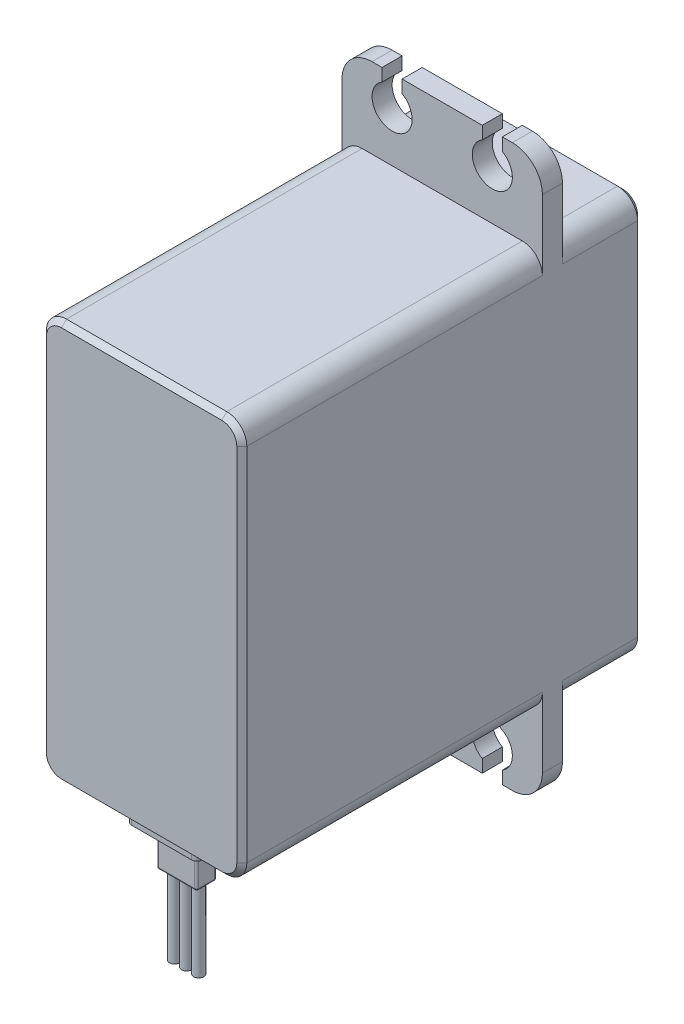
SolidWorks part; units mm, degrees
ref_plane "前视基准面" through (0, 0, 0) normal (0, 0, 1) x (1, 0, 0)
ref_plane "上视基准面" through (0, 0, 0) normal (0, 1, 0) x (1, 0, 0)
ref_plane "右视基准面" through (0, 0, 0) normal (1, 0, 0) x (0, 0, -1)
sketch "草图1" plane through (0, 0, 0) normal (0, 0, 1) x (1, 0, 0)
  line L1 (-10, -28) -> (10, -28)
  line L2 (-10, -28) -> (-10, 28)
  line L3 (-10, 28) -> (10, 28)
  line L4 (10, -28) -> (10, 28)
  line L5 (-10, -28) -> (10, 28) construction
  line L6 (-10, 28) -> (10, -28) construction
  point P0 (0, 0)
  dimension "D1" = 20
  dimension "D2" = 56
extrude "凸台-拉伸1" add sketch "草图1" along normal blind 40
sketch "草图2" plane through (0, 0, 40) normal (0, 0, 1) x (1, 0, 0)
  line L0 (10, -28) -> (10, 28) construction
  line L1 (-10, -20) -> (10, -20)
  line L2 (-10, -20) -> (-10, 20)
  line L3 (-10, 20) -> (10, 20)
  line L4 (10, -20) -> (10, 20)
  line L5 (-10, -20) -> (10, 20) construction
  line L6 (-10, 20) -> (10, -20) construction
  point P0 (0, 0)
  dimension "D1" = 40
extrude "切除-拉伸1" cut sketch "草图2" against normal blind 30 flip side to cut
extrude "切除-拉伸2" cut sketch "草图2<2>" along normal blind 8 from surface flip side to cut contours L2 L3 L4 L1 starting at face at (0, 0, 0)
sketch "草图2<2>" plane through (0, 0, 40) normal (0, 0, 1) x (1, 0, 0) same geometry as "草图2"
sketch "草图3" plane through (0, 0, 10) normal (0, 0, 1) x (1, 0, 0)
  line L0 (4, 26.7321) -> (4, 28)
  line L1 (10, 28) -> (-10, 28) construction
  line L2 (4, 28) -> (6, 28)
  line L3 (6, 28) -> (6, 26.7321)
  line L4 (5, 25) -> (5, 28) construction
  line L5 (10, 20) -> (10, 28) construction
  line L6 (-6, 26.7321) -> (-6, 28)
  line L7 (-6, 28) -> (-4, 28)
  line L8 (-4, 28) -> (-4, 26.7321)
  line L9 (0, 0) -> (15.7926, 0) construction
  line L10 (5, -25) -> (5, -28) construction
  line L11 (-4, -28) -> (-4, -26.7321)
  line L12 (-6, -28) -> (-4, -28)
  line L13 (-6, -26.7321) -> (-6, -28)
  line L14 (6, -28) -> (6, -26.7321)
  line L15 (4, -28) -> (6, -28)
  line L16 (4, -26.7321) -> (4, -28)
  arc A0 (4, 26.7321) -> (6, 26.7321) centre (5, 25) ccw
  arc A1 (-6, 26.7321) -> (-4, 26.7321) centre (-5, 25) ccw
  arc A2 (-6, -26.7321) -> (-4, -26.7321) centre (-5, -25) cw
  arc A3 (4, -26.7321) -> (6, -26.7321) centre (5, -25) cw
  dimension "D1" = 2
  dimension "D2" = 3
  dimension "D3" = 2
  dimension "D4" = 4
  dimension "D6" = 10
  dimension "D5" = 2
extrude "切除-拉伸3" cut sketch "草图3" against normal through all
sketch "草图4" plane through (0, -20, 0) normal (0, -1, 0) x (1, 0, 0)
  line L0 (-10, 40) -> (10, 40) construction
  line L1 (-3.5, 33) -> (3.5, 33)
  line L2 (-3.5, 33) -> (-3.5, 38)
  line L3 (-3.5, 38) -> (3.5, 38)
  line L4 (3.5, 33) -> (3.5, 38)
  line L5 (-3.5, 33) -> (3.5, 38) construction
  line L6 (-3.5, 38) -> (3.5, 33) construction
  point P0 (0, 35.5)
  dimension "D1" = 7
  dimension "D2" = 5
  dimension "D3" = 2
extrude "凸台-拉伸2" add sketch "草图4" along normal blind 2
sketch "草图5" plane through (0, -22, 0) normal (0, -1, 0) x (1, 0, 0)
  line L0 (-3.5, 38) -> (3.5, 33) construction
  line L1 (-2, 34.5) -> (2, 34.5)
  line L2 (-2, 34.5) -> (-2, 36.5)
  line L3 (-2, 36.5) -> (2, 36.5)
  line L4 (2, 34.5) -> (2, 36.5)
  line L5 (-2, 34.5) -> (2, 36.5) construction
  line L6 (-2, 36.5) -> (2, 34.5) construction
  line L7 (3.5, 38) -> (-3.5, 33) construction
  point P0 (0, 35.5)
  dimension "D1" = 4
  dimension "D2" = 2
extrude "凸台-拉伸3" add sketch "草图5" along normal blind 4
sketch "草图6" plane through (0, -26, 0) normal (0, -1, 0) x (1, 0, 0)
  line L0 (2, 34.5) -> (2, 36.5) construction
  line L1 (-2, 35.5) -> (2, 35.5) construction
  line L2 (-2, 36.5) -> (-2, 34.5) construction
  line L3 (2, 34.5) -> (2, 36.5) construction
  circle A0 centre (1.2, 35.5) radius 0.5
  circle A1 centre (0, 35.5) radius 0.5
  circle A2 centre (-1.2, 35.5) radius 0.5
  dimension "D1" = 1
  dimension "D2" = 0.8
  dimension "D4" = 1.2
  dimension "D3" = 1.2
extrude "凸台-拉伸4" add sketch "草图6" along normal blind 8
sketch "草图7" plane through (0, 0, 0) normal (0, 0, -1) x (-1, 0, 0)
  line L0 (-10, -20) -> (10, -20) construction
  circle A0 centre (0, -12) radius 6
  dimension "D1" = 12
  dimension "D2" = 8
extrude "凸台-拉伸5" add sketch "草图7" along normal blind 2
sketch "草图8" plane through (0, 0, -2) normal (0, 0, -1) x (-1, 0, 0)
  circle A0 centre (0, -12) radius 5
  dimension "D1" = 10
extrude "切除-拉伸4" cut sketch "草图8" against normal blind 0.8
sketch "草图9" plane through (0, 0, -1.2) normal (0, 0, -1) x (-1, 0, 0)
  circle A0 centre (0, -12) radius 2.5
  dimension "D1" = 5
extrude "切除-拉伸5" cut sketch "草图9" against normal blind 4
sketch "草图10" plane through (0, 0, 2.8) normal (0, 0, -1) x (-1, 0, 0)
  circle A1 centre (0, -12) radius 2.5
  circle A2 centre (0, -12) radius 2.5
  dimension "D1" = 0
extrude "凸台-拉伸6" add sketch "草图10" along normal blind 10 separate body
sketch "草图11" plane through (0, 0, -7.2) normal (0, 0, -1) x (-1, 0, 0)
  line L0 (0, -12) -> (0, -9.5) construction
  line L1 (0, -10) -> (-0.2796, -9.5157)
  line L2 (0, -10) -> (0.2796, -9.5157)
  line L3 (0.618, -10.0979) -> (0.5018, -9.5509)
  line L4 (0.618, -10.0979) -> (1.0336, -9.7237)
  line L5 (1.1756, -10.382) -> (1.234, -9.8258)
  line L6 (1.1756, -10.382) -> (1.6865, -10.1545)
  line L7 (1.618, -10.8244) -> (1.8455, -10.3135)
  line L8 (1.618, -10.8244) -> (2.1742, -10.766)
  line L9 (1.9021, -11.382) -> (2.2763, -10.9664)
  line L10 (1.9021, -11.382) -> (2.4491, -11.4982)
  line L11 (2, -12) -> (2.4843, -11.7204)
  line L12 (2, -12) -> (2.4843, -12.2796)
  line L13 (1.9021, -12.618) -> (2.4491, -12.5018)
  line L14 (1.9021, -12.618) -> (2.2763, -13.0336)
  line L15 (1.618, -13.1756) -> (2.1742, -13.234)
  line L16 (1.618, -13.1756) -> (1.8455, -13.6865)
  line L17 (1.1756, -13.618) -> (1.6865, -13.8455)
  line L18 (1.1756, -13.618) -> (1.234, -14.1742)
  line L19 (0.618, -13.9021) -> (1.0336, -14.2763)
  line L20 (0.618, -13.9021) -> (0.5018, -14.4491)
  line L21 (0, -14) -> (0.2796, -14.4843)
  line L22 (0, -14) -> (-0.2796, -14.4843)
  line L23 (-0.618, -13.9021) -> (-0.5018, -14.4491)
  line L24 (-0.618, -13.9021) -> (-1.0336, -14.2763)
  line L25 (-1.1756, -13.618) -> (-1.234, -14.1742)
  line L26 (-1.1756, -13.618) -> (-1.6865, -13.8455)
  line L27 (-1.618, -13.1756) -> (-1.8455, -13.6865)
  line L28 (-1.618, -13.1756) -> (-2.1742, -13.234)
  line L29 (-1.9021, -12.618) -> (-2.2763, -13.0336)
  line L30 (-1.9021, -12.618) -> (-2.4491, -12.5018)
  line L31 (-2, -12) -> (-2.4843, -12.2796)
  line L32 (-2, -12) -> (-2.4843, -11.7204)
  line L33 (-1.9021, -11.382) -> (-2.4491, -11.4982)
  line L34 (-1.9021, -11.382) -> (-2.2763, -10.9664)
  line L35 (-1.618, -10.8244) -> (-2.1742, -10.766)
  line L36 (-1.618, -10.8244) -> (-1.8455, -10.3135)
  line L37 (-1.1756, -10.382) -> (-1.6865, -10.1545)
  line L38 (-1.1756, -10.382) -> (-1.234, -9.8258)
  line L39 (-0.618, -10.0979) -> (-1.0336, -9.7237)
  line L40 (-0.618, -10.0979) -> (-0.5018, -9.5509)
  circle A0 centre (0, -12) radius 2.5 construction
  arc A1 (0.2796, -9.5157) -> (-0.2796, -9.5157) centre (0, -12) ccw
  arc A2 (1.0336, -9.7237) -> (0.5018, -9.5509) centre (0, -12) ccw
  arc A3 (1.6865, -10.1545) -> (1.234, -9.8258) centre (0, -12) ccw
  arc A4 (2.1742, -10.766) -> (1.8455, -10.3135) centre (0, -12) ccw
  arc A5 (2.4491, -11.4982) -> (2.2763, -10.9664) centre (0, -12) ccw
  arc A6 (2.4843, -12.2796) -> (2.4843, -11.7204) centre (0, -12) ccw
  arc A7 (2.2763, -13.0336) -> (2.4491, -12.5018) centre (0, -12) ccw
  arc A8 (1.8455, -13.6865) -> (2.1742, -13.234) centre (0, -12) ccw
  arc A9 (1.234, -14.1742) -> (1.6865, -13.8455) centre (0, -12) ccw
  arc A10 (0.5018, -14.4491) -> (1.0336, -14.2763) centre (0, -12) ccw
  arc A11 (-0.2796, -14.4843) -> (0.2796, -14.4843) centre (0, -12) ccw
  arc A12 (-1.0336, -14.2763) -> (-0.5018, -14.4491) centre (0, -12) ccw
  arc A13 (-1.6865, -13.8455) -> (-1.234, -14.1742) centre (0, -12) ccw
  arc A14 (-2.1742, -13.234) -> (-1.8455, -13.6865) centre (0, -12) ccw
  arc A15 (-2.4491, -12.5018) -> (-2.2763, -13.0336) centre (0, -12) ccw
  arc A16 (-2.4843, -11.7204) -> (-2.4843, -12.2796) centre (0, -12) ccw
  arc A17 (-2.2763, -10.9664) -> (-2.4491, -11.4982) centre (0, -12) ccw
  arc A18 (-1.8455, -10.3135) -> (-2.1742, -10.766) centre (0, -12) ccw
  arc A19 (-1.234, -9.8258) -> (-1.6865, -10.1545) centre (0, -12) ccw
  arc A20 (-0.5018, -9.5509) -> (-1.0336, -9.7237) centre (0, -12) ccw
  point P66 (0, -12)
  dimension "D1" = 2
  dimension "D2" = 60
  dimension "D3" = 20
extrude "切除-拉伸6" cut sketch "草图11" against normal through all
sketch "草图12" plane through (0, 0, 0) normal (1, 0, 0) x (0, 0, -1)
  line L0 (7.2, -10) -> (7.2, -8)
  line L1 (7.2, -10.382) -> (7.2, -9.8258) construction
  line L2 (7.2, -8) -> (6.0453, -8)
  line L3 (6.0453, -8) -> (7.2, -10)
  dimension "D1" = 30
  dimension "D2" = 2
revolve "切除-旋转1" cut sketch "草图12" angle 360 about axis through (0, -12, -7.2) along (0, 0, 1)
ref_plane "基准面1" through (0, 0, -2.2) normal (0, 0, 1) x (1, 0, 0)
mirror "镜向1" about plane through (0, 0, -2.2) normal (0, 0, 1) of "切除-旋转1"
hole_wizard "M2 螺纹孔1" positions "3D草图1" profile "草图13" tap size "M2" standard "GB"
sketch3d "3D草图1"
  arc A0 (0.618, -13.9021, -7.2) -> (0, -14, -7.2) centre (0, -12, -7.2) ccw construction
  point P0 (0, -12, -7.2)
  point P7 (0, -12, -9.2)
sketch "草图13" plane through (0, -12, -7.2) normal (1, 0, 0) x (0, 1, 0)
  line L0 (0, 0) -> (0, 10.4807)
  line L1 (0, 10.4807) -> (0.8, 10)
  line L2 (0.8, 10) -> (0.8, 0)
  line L5 (0.8, 0) -> (0, 0)
  line L10 (0, 10.4807) -> (-0.8, 10) construction
  line L11 (0, -6.35) -> (0, 107.95) construction
  dimension "螺纹孔钻头直径" = 1.6
  dimension "螺纹孔钻头深度" = 10
  dimension "导头角度" = 118
cosmetic thread "孔螺蚊线1" parameters "D1"=4, "D2"=2
fillet "圆角1" radius 3 4 edges at (-10, -28, 9) (10, -28, 9) (-10, 28, 9) (10, 28, 9)
fillet "圆角2" radius 2 8 edges at (-10, 20, 4) (-10, -20, 4) (10, -20, 4) (10, 20, 4) (-10, -20, 25) (-10, 20, 25) (10, -20, 25) (10, 20, 25)
fillet "圆角3" radius 0.5 4 edges at (3.5, -21, 33) (-3.5, -21, 33) (-3.5, -21, 38) (3.5, -21, 38)
fillet "圆角4" radius 0.2 8 edges at (2, -26, 35.5) (0, -26, 36.5) (-2, -26, 35.5) (0, -26, 34.5) (2, -24, 34.5) (-2, -24, 34.5) (-2, -24, 36.5) (2, -24, 36.5)
chamfer "倒角1" distance 0.5 angle 45 17 edges at (-6, -12, -2) (-10, 0, 0) (-9.4142, -19.4142, 0) (-9.4142, 19.4142, 0) (0, -20, 0) (0, 20, 0) (9.4142, -19.4142, 0) (9.4142, 19.4142, 0) (10, 0, 0) (0, -20, 40) (9.4142, -19.4142, 40) (-9.4142, -19.4142, 40) (10, 0, 40) (-10, 0, 40) (9.4142, 19.4142, 40) (-9.4142, 19.4142, 40) (0, 20, 40)
move or copy body "实体-移动/复制1" [suppressed] bodies to move or copy 120 121
equation "\"0。8\"=0.715841"
